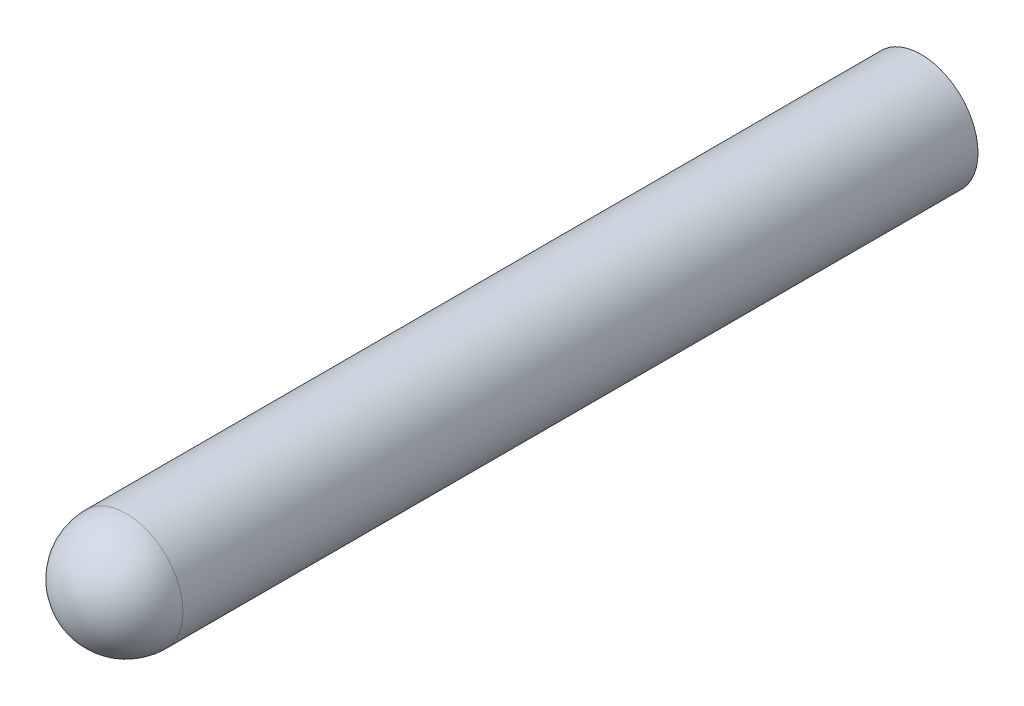
SolidWorks part; units mm, degrees
ref_plane "Front Plane" through (0, 0, 0) normal (0, 0, 1) x (1, 0, 0)
ref_plane "Top Plane" through (0, 0, 0) normal (0, 1, 0) x (1, 0, 0)
ref_plane "Right Plane" through (0, 0, 0) normal (1, 0, 0) x (0, 0, -1)
sketch "Sketch1" plane through (0, 0, 0) normal (0, 0, 1) x (1, 0, 0)
  circle A0 centre (0, 0) radius 2
extrude "Boss-Extrude1" add sketch "Sketch1" along normal blind 30
fillet "Fillet1" radius 2 1 edges at (2, 0, 30)
